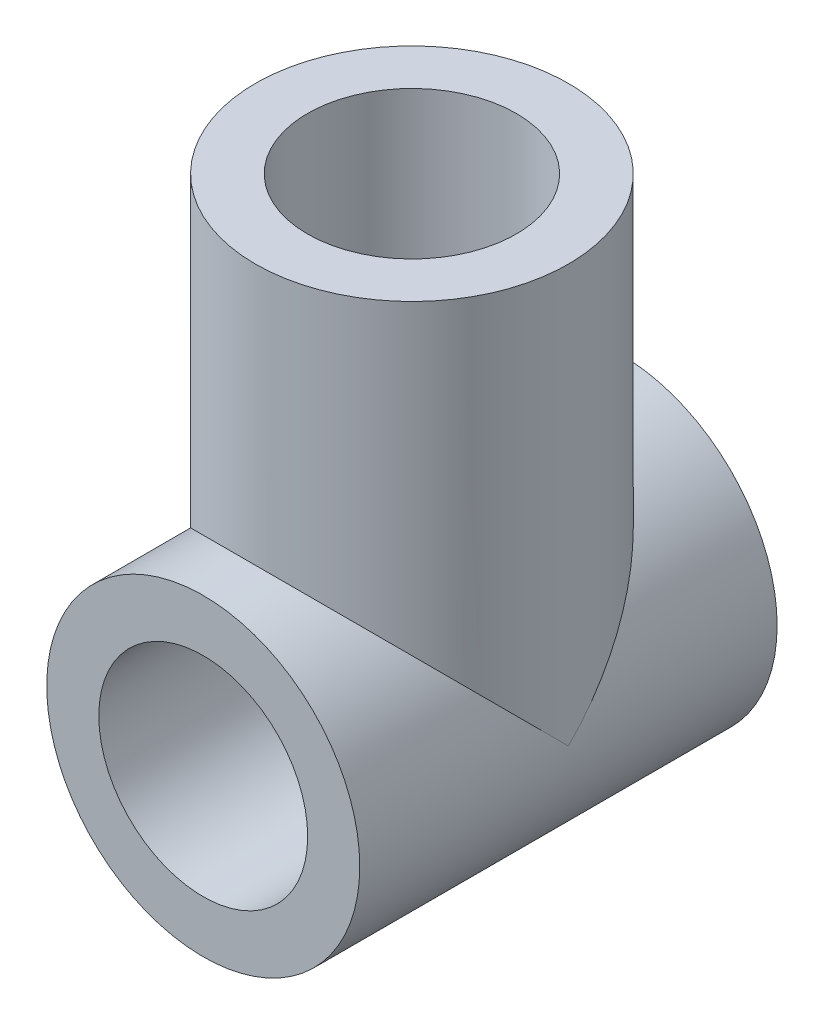
SolidWorks part; units mm, degrees
ref_plane "Front Plane" through (0, 0, 0) normal (0, 0, 1) x (1, 0, 0)
ref_plane "Top Plane" through (0, 0, 0) normal (0, 1, 0) x (1, 0, 0)
ref_plane "Right Plane" through (0, 0, 0) normal (1, 0, 0) x (0, 0, -1)
sketch "Sketch1" plane through (0, 0, 0) normal (0, 0, 1) x (1, 0, 0)
  circle A0 centre (0, 0) radius 7.5
  dimension "D1" = 15
ref_plane "Plane1" through (0, 20, 0) normal (0, 1, 0) x (1, 0, 0)
sketch "Sketch3" plane through (0, 20, 0) normal (0, 1, 0) x (1, 0, 0)
  circle A0 centre (0, 0) radius 7.5
  dimension "D1" = 15
extrude "Boss-Extrude1" add sketch "Sketch1" along normal blind 10 and the other way blind 10 contours A0
extrude "Boss-Extrude2" add sketch "Sketch3" against normal blind 20 contours A0
sketch "Sketch4" plane through (0, 0, 10) normal (0, 0, 1) x (1, 0, 0)
  circle A0 centre (0, 0) radius 5.005
  dimension "D1" = 10.01
extrude "Cut-Extrude2" cut sketch "Sketch4" against normal blind 23 contours A0
sketch "Sketch5" plane through (0, 20, 0) normal (0, 1, 0) x (1, 0, 0)
  circle A0 centre (0, 0) radius 5.005
  dimension "D1" = 10.01
extrude "Cut-Extrude3" cut sketch "Sketch5" against normal blind 9
